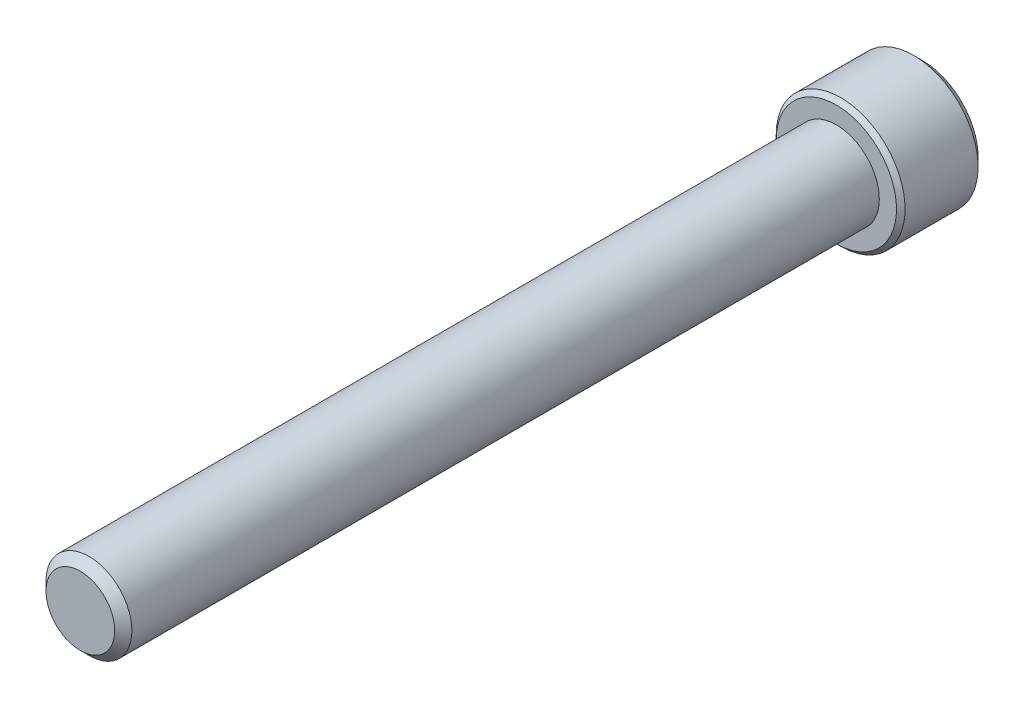
SolidWorks part; units mm, degrees
material "Alloy Steel"
ref_plane "Front Plane" through (0, 0, 0) normal (0, 0, 1) x (1, 0, 0)
ref_plane "Top Plane" through (0, 0, 0) normal (0, 1, 0) x (1, 0, 0)
ref_plane "Right Plane" through (0, 0, 0) normal (1, 0, 0) x (0, 0, -1)
sketch "Sketch1" plane through (0, 0, 0) normal (0, 0, 1) x (1, 0, 0)
  line L0 (0, 3.9688) -> (0, -3.9688) construction
  circle A0 centre (0, 0) radius 3.9688
  dimension "OD" = 7.9375
extrude "Extrude1" add sketch "Sketch1" against normal blind 69.85
sketch "Sketch2" plane through (0, 0, 0) normal (0, 0, 1) x (1, 0, 0)
  circle A0 centre (0, 0) radius 3.9688 construction
  circle A1 centre (0, 0) radius 3.9688
curve "Helix/Spiral1" pitch 1.0583 height 30.6917 turns 29 parameters "pitch"=1.0583
chamfer "Chamfer3" distance 0.7937 angle 45 1 edges at (3.9688, 0, 0)
sketch "Sketch3" plane through (0, 0, 0) normal (1, 0, 0) x (0, 0, -1)
  line L0 (-0.926, 3.9688) -> (-0.5292, 3.2813)
  line L1 (-0.5292, 3.2813) -> (-0.3969, 3.2813)
  line L2 (-0.3969, 3.2813) -> (0, 3.9688)
  line L3 (-0.926, 3.9688) -> (0, 3.9688)
  line L4 (-0.463, 3.9688) -> (-0.463, 3.2813) construction
  line L5 (-0.7276, 3.625) -> (-0.1984, 3.625) construction
  line L6 (0, 3.9688) -> (0, -3.9688) construction
  dimension "D1" = 0.1323
  dimension "D2" = 0.5292
  dimension "D3" = 60
sweep "Cut-Sweep1" [suppressed] cut profiles "Sketch3" path "Helix/Spiral1"
sketch "Sketch5" plane through (0, 0, 0) normal (1, 0, 0) x (0, 0, -1)
  line L1 (69.85, 3.9688) -> (28.575, 3.9688)
  line L2 (69.85, 3.9688) -> (69.85, 0)
  line L3 (69.85, 0) -> (28.575, 0)
  line L4 (28.575, 3.9688) -> (28.575, 0) construction
  line L6 (0, 0) -> (9.9695, 0) construction
  line L8 (28.575, 3.9688) -> (24.6062, 0)
  line L9 (24.6062, 0) -> (28.575, 0)
  line L10 (69.85, -3.9688) -> (69.85, 3.9688) construction
  dimension "Thread min" = 28.575
  dimension "D1" = 45
revolve "partially thread" add sketch "Sketch5" angle 360 about L6
sketch "Sketch6" plane through (0, 0, -69.85) normal (0, 0, -1) x (-1, 0, 0)
  circle A0 centre (0, 0) radius 5.9531
  dimension "head dia" = 11.9062
extrude "Extrude2" add sketch "Sketch6" along normal blind 7.9375
sketch "Sketch7" plane through (0, 0, -77.7875) normal (0, 0, -1) x (-1, 0, 0)
  line L1 (0, 3.6662) -> (-3.175, 1.8331)
  line L2 (-3.175, 1.8331) -> (-3.175, -1.8331)
  line L3 (-3.175, -1.8331) -> (0, -3.6662)
  line L4 (0, -3.6662) -> (3.175, -1.8331)
  line L5 (3.175, -1.8331) -> (3.175, 1.8331)
  line L6 (3.175, 1.8331) -> (0, 3.6662)
  circle A0 centre (0, 0) radius 3.175 construction
  dimension "hex dia" = 6.35
extrude "Cut-Extrude1" cut sketch "Sketch7" against normal blind 4.7625
sketch "Sketch8" plane through (0, 0, -77.7875) normal (0, 0, -1) x (-1, 0, 0)
  circle A0 centre (0, 0) radius 3.6662
extrude "Cut-Extrude2" cut sketch "Sketch8" against normal blind 0.7937 draft 45
chamfer "Chamfer1" distance 0.7937 angle 45 1 edges at (-5.9531, 0, -77.7875)
chamfer "Chamfer2" distance 0.3969 angle 45 1 edges at (-5.9531, 0, -69.85)
sketch "Sketch9" plane through (0, 0, 0) normal (1, 0, 0) x (0, 0, -1)
  line L0 (0, 3.9688) -> (0, -3.9688) construction
  line L1 (5.8208, 3.9688) -> (5.8208, -3.9688) construction
  line L2 (69.85, 5.9531) -> (69.85, -5.9531) construction
  line L3 (77.7875, 5.9531) -> (77.7875, -5.9531) construction
  line L4 (77.7875, 0) -> (0, 0) construction
  line L5 (61.6852, 3.9688) -> (61.6852, -3.9688) construction
  dimension "D1" = 5.8208
  dimension "D2" = 7.9375
  dimension "D3" = 11.9062
  dimension "D4" = 69.85
  dimension "Thread Length" = 61.6852
move or copy body "Body-Move/Copy1" [suppressed] bodies to move or copy 107
equation "\"D3@Helix/Spiral1\" = \"Thread min@Sketch5\"+(\"pitch@Helix/Spiral1\"*2)"
equation "\"D1@Sketch3\" = \"pitch@Helix/Spiral1\"*.125"
equation "\"D2@Sketch3\" = \"pitch@Helix/Spiral1\"*.5"
equation "\"D1@Cut-Extrude1\" = \"hex dia@Sketch7\"*.75"
equation "\"D1@Chamfer1\" = \"head depth@Extrude2\"/10"
equation "\"D1@Sketch9\" = \"pitch@Helix/Spiral1\"*5.5"
equation "\"D1@Chamfer2\" = \"D1@Chamfer1\"/2"
equation "\"D1@Cut-Extrude2\" = \"D1@Chamfer2\"*2"
equation "\"D1@Chamfer3\" = \"pitch@Helix/Spiral1\"*.750"
equation "\"D2@Sketch9\" = \"head depth@Extrude2\""
equation "\"D3@Sketch9\" = \"head dia@Sketch6\""
equation "\"D4@Sketch9\" = \"screw length@Extrude1\""
